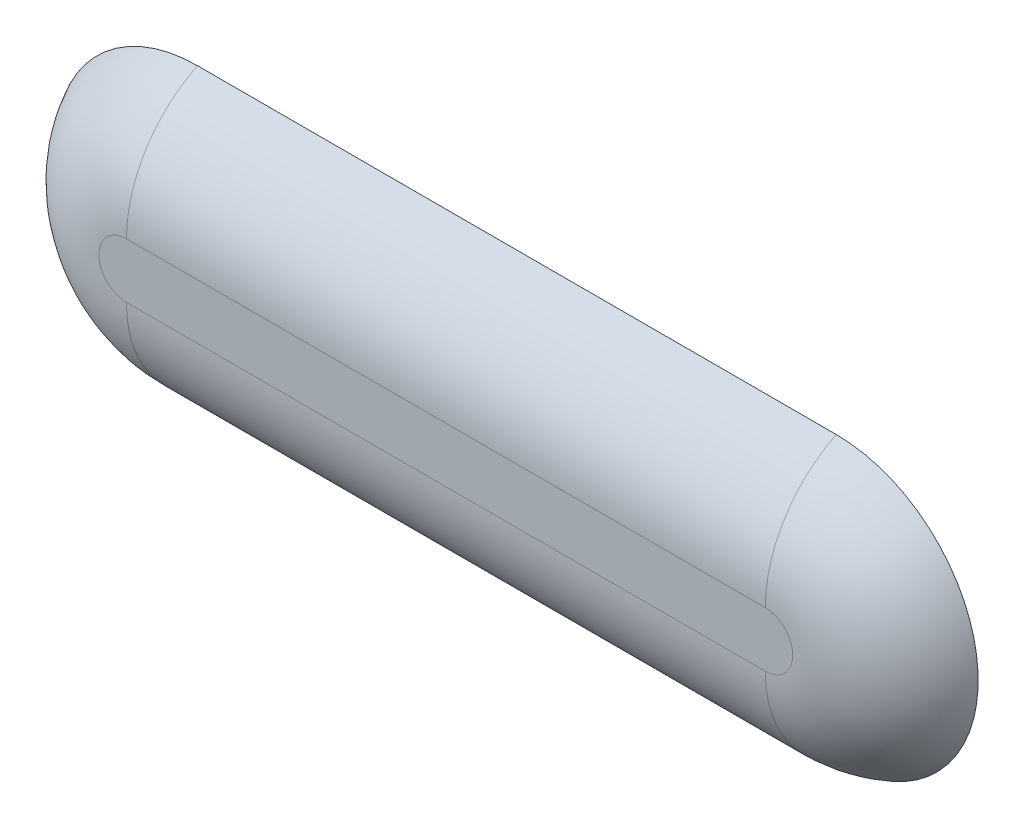
SolidWorks part; units mm, degrees
ref_plane "Front Plane" through (0, 0, 0) normal (0, 0, 1) x (1, 0, 0)
ref_plane "Top Plane" through (0, 0, 0) normal (0, 1, 0) x (1, 0, 0)
ref_plane "Right Plane" through (0, 0, 0) normal (1, 0, 0) x (0, 0, -1)
sketch "Sketch1" plane through (0, 0, 0) normal (0, 0, 1) x (1, 0, 0)
  line L0 (0, 0) -> (2.286, 0) construction
  line L1 (0, 0.508) -> (2.286, 0.508)
  line L2 (0, -0.508) -> (2.286, -0.508)
  arc A0 (0, 0.508) -> (0, -0.508) centre (0, 0) ccw
  arc A1 (2.286, -0.508) -> (2.286, 0.508) centre (2.286, 0) ccw
  point P3 (1.143, 0)
  dimension "D1" = 2.286
  dimension "D2" = 1.016
extrude "Boss-Extrude1" add sketch "Sketch1" along normal blind 0.254
fillet "Fillet5" radius 0.4572 4 edges at (-0.508, 0, 0.254) (1.143, -0.508, 0.254) (2.794, 0, 0.254) (1.143, 0.508, 0.254)
